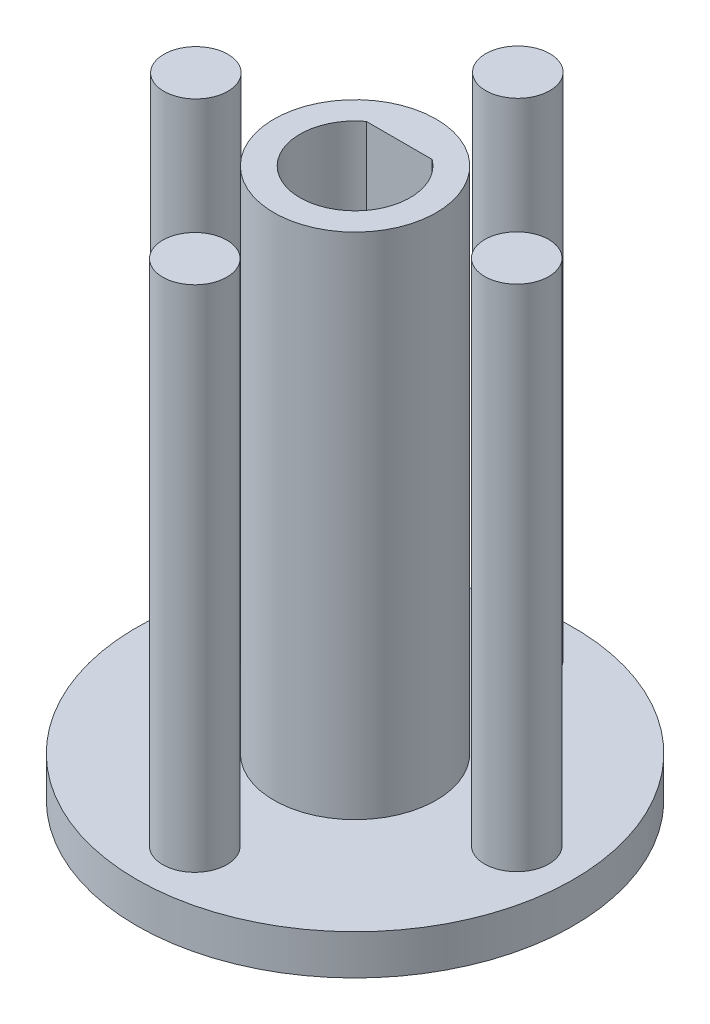
SolidWorks part; units mm, degrees
ref_plane "Front Plane" through (0, 0, 0) normal (0, 0, 1) x (1, 0, 0)
ref_plane "Top Plane" through (0, 0, 0) normal (0, 1, 0) x (1, 0, 0)
ref_plane "Right Plane" through (0, 0, 0) normal (1, 0, 0) x (0, 0, -1)
sketch "Sketch3" plane through (0, 0, 0) normal (0, 1, 0) x (1, 0, 0)
  line L0 (-7.9995, 0.0532) -> (0.009, 8.1156) construction
  line L1 (0.009, 8.1156) -> (8.0177, 0.0533) construction
  line L2 (8.0177, 0.0533) -> (0.0092, -8.0091) construction
  line L3 (0.0092, -8.0091) -> (-7.9995, 0.0532) construction
  line L7 (18.7783, 0.0532) -> (-25.5315, 0.0532) construction
  line L8 (9.7482, 0.0532) -> (10.8982, 0.0532)
  line L9 (-1.6438, 2.2047) -> (1.6438, 2.2047)
  line L11 (0.009, -13.1564) -> (0.009, 16.0208) construction
  circle A0 centre (0, 0) radius 10.9
  circle A1 centre (0.009, 8.1156) radius 1.6
  circle A2 centre (8.0177, 0.0533) radius 1.6
  circle A3 centre (0.0092, -8.0091) radius 1.6
  circle A4 centre (-7.9995, 0.0532) radius 1.6
  circle A5 centre (0, 0) radius 4.05
  arc A6 (-1.6438, 2.2047) -> (1.6438, 2.2047) centre (0, 0) ccw
  dimension "D1" = 21.8
extrude "Boss-Extrude1" add sketch "Sketch3" along normal blind 27.4 contours A4 | A3 | A2 | A1 | A6 L9 | A5
extrude "Boss-Extrude2" add sketch "Sketch3<17>" along normal blind 2 contours A0
sketch "Sketch3<17>" plane through (0, 0, 0) normal (0, 1, 0) x (1, 0, 0) same geometry as "Sketch3"
ref_plane "Plane1" through (1.6438, 27.4, -2.2047) normal (-0.8017, 0, -0.5977) x (-0.5977, 0, 0.8017)
